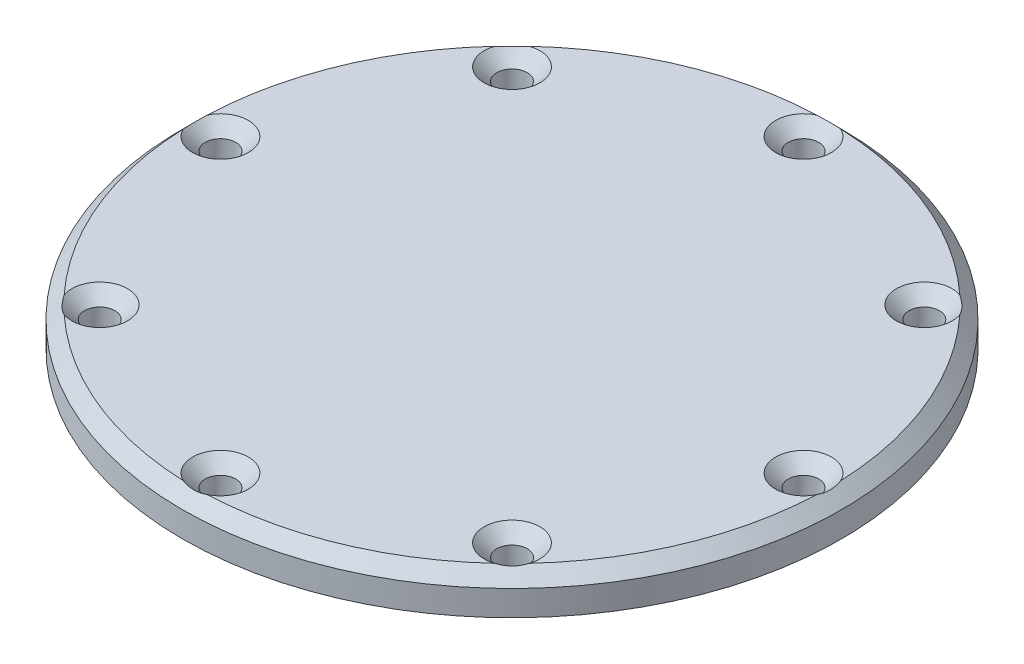
SolidWorks part; units mm, degrees
ref_plane "Спереди" through (0, 0, 0) normal (0, 0, 1) x (1, 0, 0)
ref_plane "Сверху" through (0, 0, 0) normal (0, 1, 0) x (1, 0, 0)
ref_plane "Справа" through (0, 0, 0) normal (1, 0, 0) x (0, 0, -1)
sketch "Эскиз1" plane through (0, 0, 0) normal (0, 0, 1) x (1, 0, 0)
  line L0 (0, 0) -> (0, 14224.778) construction
  line L1 (0, 0) -> (26, 0)
  line L2 (26, 0) -> (26, 2)
  line L3 (26, 2) -> (25, 3)
  line L4 (25, 3) -> (0, 3)
  line L5 (0, 3) -> (0, 0)
  dimension "D1" = 3
  dimension "D2" = 52
  dimension "D3" = 1
  dimension "D4" = 45
revolve "Повернуть1" add sketch "Эскиз1" angle 360 about L0
hole_wizard "Зенковка для винта с потайной головкой M21" positions "Эскиз2" profile "Эскиз3" countersink size "M2" standard "HASCO Metric" end condition through all
sketch "Эскиз2" plane through (0, 3, 0) normal (0, 1, 0) x (1, 0, 0)
  line L2 (0, 0) -> (18.3848, 18.3848) construction
  line L4 (0, 0) -> (0, 26) construction
  circle A1 centre (0, 0) radius 26 construction
  circle A2 centre (0, 0) radius 23 construction
  point P0 (16.2635, 16.2635)
  point P27 (16.587, 15.9334)
  point P28 (16.2635, 16.2635)
  dimension "D2" = 46
  dimension "D1" = 45
sketch "Эскиз3" plane through (16.2635, 3, -16.2635) normal (1, 0, 0) x (0, 0, 1)
  line L0 (0, 0) -> (0, 3)
  line L1 (0, 3) -> (1.2, 3)
  line L2 (1.2, 3) -> (1.2, 1)
  line L3 (1.2, 1) -> (2.2, 0)
  line L5 (2.2, 0) -> (0, 0)
  line L6 (-1.2, 1) -> (-2.2, 0) construction
  line L11 (0, -6.35) -> (0, 107.95) construction
  dimension "Диаметр сквозного отверстия" = 2.4
  dimension "Глубина сквозного отверстия" = 3
  dimension "Диаметр передней зенковки" = 4.4
  dimension "Угол передней зенковки" = 90
pattern_circular "Круговой массив1" count 8 over 360 about axis through (0, 0, 0) along (0, -1, 0) of "Зенковка для винта с потайной головкой M21" reverse direction yes
